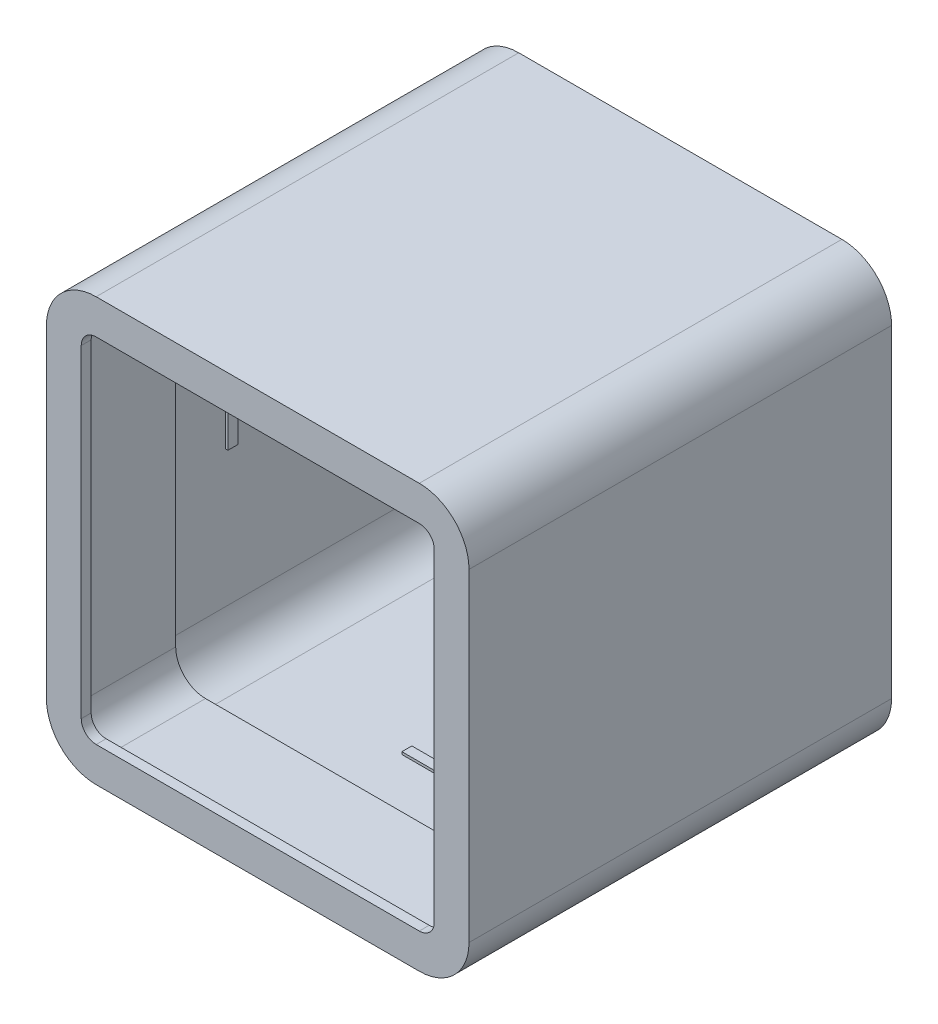
SolidWorks part; units mm, degrees
material "ABS-White"
ref_plane "Front Plane" through (0, 0, 0) normal (0, 0, 1) x (1, 0, 0)
ref_plane "Top Plane" through (0, 0, 0) normal (0, 1, 0) x (1, 0, 0)
ref_plane "Right Plane" through (0, 0, 0) normal (1, 0, 0) x (0, 0, -1)
sketch "Sketch1" plane through (0, 0, 0) normal (0, 0, 1) x (1, 0, 0)
  line L1 (-42.5, -42.5) -> (42.5, -42.5)
  line L2 (-42.5, -42.5) -> (-42.5, 42.5)
  line L3 (-42.5, 42.5) -> (42.5, 42.5)
  line L4 (42.5, -42.5) -> (42.5, 42.5)
  line L5 (-42.5, -42.5) -> (42.5, 42.5) construction
  line L6 (-42.5, 42.5) -> (42.5, -42.5) construction
  point P0 (0, 0)
  dimension "D1" = 85
  dimension "D2" = 85
extrude "Boss-Extrude1" add sketch "Sketch1" along normal blind 85
fillet "Fillet1" radius 10 4 edges at (-42.5, 42.5, 42.5) (-42.5, -42.5, 42.5) (42.5, -42.5, 42.5) (42.5, 42.5, 42.5)
shell "Shell1" thickness 2
sketch "Sketch2" plane through (0, 0, 85) normal (0, 0, 1) x (1, 0, 0)
  line L8 (32.5, 35.5) -> (-32.5, 35.5)
  line L9 (-35.5, 32.5) -> (-35.5, -32.5)
  line L10 (-32.5, -35.5) -> (32.5, -35.5)
  line L11 (35.5, -32.5) -> (35.5, 32.5)
  line L12 (32.5, 35.5) -> (-32.5, 35.5)
  line L13 (-35.5, 32.5) -> (-35.5, -32.5)
  line L14 (-32.5, -35.5) -> (32.5, -35.5)
  line L15 (35.5, -32.5) -> (35.5, 32.5)
  arc A8 (-32.5, 35.5) -> (-35.5, 32.5) centre (-32.5, 32.5) ccw
  arc A9 (-35.5, -32.5) -> (-32.5, -35.5) centre (-32.5, -32.5) ccw
  arc A10 (32.5, -35.5) -> (35.5, -32.5) centre (32.5, -32.5) ccw
  arc A11 (35.5, 32.5) -> (32.5, 35.5) centre (32.5, 32.5) ccw
  arc A12 (-32.5, 35.5) -> (-35.5, 32.5) centre (-32.5, 32.5) ccw
  arc A13 (-35.5, -32.5) -> (-32.5, -35.5) centre (-32.5, -32.5) ccw
  arc A14 (32.5, -35.5) -> (35.5, -32.5) centre (32.5, -32.5) ccw
  arc A15 (35.5, 32.5) -> (32.5, 35.5) centre (32.5, 32.5) ccw
  dimension "D1" = 7
extrude "Cut-Extrude1" cut sketch "Sketch2" against normal up to next contours L12 A12 L13 A13 L14 A14 L15 A15
sketch "Sketch3" plane through (0, 0, 83) normal (0, 0, -1) x (-1, 0, 0)
  line L20 (-32.5, 40.5) -> (32.5, 40.5) construction
  line L21 (-40.5, -32.5) -> (-40.5, 32.5) construction
  line L22 (-32.5, 40.5) -> (32.5, 40.5)
  line L23 (-40.5, -32.5) -> (-40.5, 32.5)
  line L24 (38.5, -32.5) -> (38.5, 32.5)
  line L25 (-32.5, -38.5) -> (32.5, -38.5)
  line L26 (-38.5, 32.5) -> (-38.5, -32.5)
  line L27 (32.5, 38.5) -> (-32.5, 38.5)
  line L28 (38.5, -32.5) -> (38.5, 32.5)
  line L29 (-32.5, -38.5) -> (32.5, -38.5)
  line L30 (-38.5, 32.5) -> (-38.5, -32.5)
  line L31 (32.5, 38.5) -> (-32.5, 38.5)
  line L32 (32.5, -40.5) -> (-32.5, -40.5) construction
  line L33 (40.5, 32.5) -> (40.5, -32.5) construction
  line L34 (32.5, -40.5) -> (-32.5, -40.5)
  line L35 (40.5, 32.5) -> (40.5, -32.5)
  arc A16 (-32.5, 40.5) -> (-40.5, 32.5) centre (-32.5, 32.5) ccw construction
  arc A17 (-32.5, 40.5) -> (-40.5, 32.5) centre (-32.5, 32.5) ccw
  arc A18 (-40.5, -32.5) -> (-32.5, -40.5) centre (-32.5, -32.5) ccw construction
  arc A19 (32.5, -40.5) -> (40.5, -32.5) centre (32.5, -32.5) ccw construction
  arc A20 (38.5, 32.5) -> (32.5, 38.5) centre (32.5, 32.5) ccw
  arc A21 (32.5, -38.5) -> (38.5, -32.5) centre (32.5, -32.5) ccw
  arc A22 (-38.5, -32.5) -> (-32.5, -38.5) centre (-32.5, -32.5) ccw
  arc A23 (-32.5, 38.5) -> (-38.5, 32.5) centre (-32.5, 32.5) ccw
  arc A24 (38.5, 32.5) -> (32.5, 38.5) centre (32.5, 32.5) ccw
  arc A25 (32.5, -38.5) -> (38.5, -32.5) centre (32.5, -32.5) ccw
  arc A26 (-38.5, -32.5) -> (-32.5, -38.5) centre (-32.5, -32.5) ccw
  arc A27 (-32.5, 38.5) -> (-38.5, 32.5) centre (-32.5, 32.5) ccw
  arc A28 (40.5, 32.5) -> (32.5, 40.5) centre (32.5, 32.5) ccw construction
  arc A29 (-40.5, -32.5) -> (-32.5, -40.5) centre (-32.5, -32.5) ccw
  arc A30 (32.5, -40.5) -> (40.5, -32.5) centre (32.5, -32.5) ccw
  arc A31 (40.5, 32.5) -> (32.5, 40.5) centre (32.5, 32.5) ccw
  dimension "D1" = 2
sketch "Sketch4" plane through (40.5, 0, 0) normal (-1, 0, 0) x (0, 0, 1)
  line L0 (83, -32.5) -> (83, 32.5) construction
  line L1 (49, -5) -> (51, -5)
  line L2 (49, -5) -> (49, 5)
  line L3 (49, 5) -> (51, 5)
  line L4 (51, -5) -> (51, 5)
  line L5 (49, -5) -> (51, 5) construction
  line L6 (49, 5) -> (51, -5) construction
  point P0 (50, 0)
  dimension "D1" = 32
  dimension "D2" = 2
  dimension "D3" = 10
ref_axis "Axis1" through (0, 0, -4.25) along (0, 0, 1)
extrude "Boss-Extrude2" add sketch "Sketch3" along normal blind 20
extrude "Boss-Extrude3" add sketch "Sketch4" along normal blind 0.5
pattern_circular "CirPattern1" count 4 over 360 about axis through (0, 0, -4.25) along (0, 0, 1) of "Boss-Extrude3"
ref_plane "Plane1" through (0, 0, 30) normal (0, 0, 1) x (1, 0, 0)
